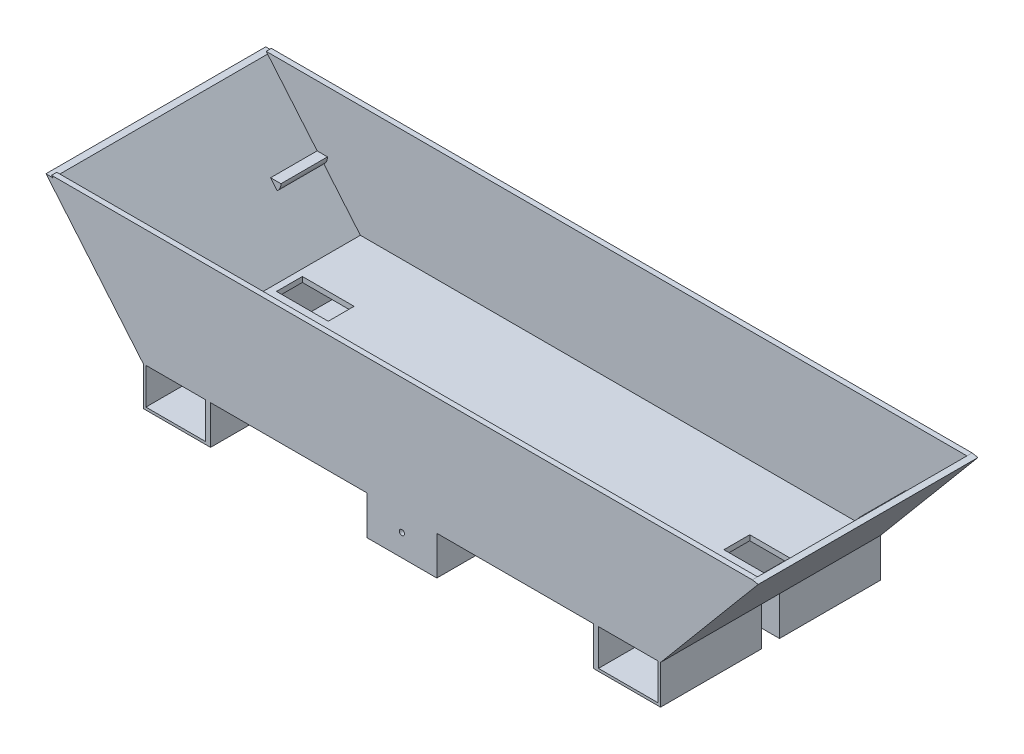
SolidWorks part; units mm, degrees
ref_plane "Plan de face" through (0, 0, 0) normal (0, 0, 1) x (1, 0, 0)
ref_plane "Plan de dessus" through (0, 0, 0) normal (0, 1, 0) x (1, 0, 0)
ref_plane "Plan de droite" through (0, 0, 0) normal (1, 0, 0) x (0, 0, -1)
sketch "Esquisse1" plane through (0, 0, 0) normal (0, 0, 1) x (1, 0, 0)
  line L0 (0, 0) -> (-200, 0)
  line L1 (0, 0) -> (37.7595, 45)
  line L2 (-200, 0) -> (-237.7595, 45)
  point P3 (0, 0)
  point P6 (-225.173, 30)
  point P7 (-225.173, 30)
  point P8 (0, 0)
  dimension "D1" = 130
  dimension "D2" = 130
  dimension "D3" = 200
  dimension "D4" = 45
  dimension "D5" = 45
extrude "Extru.-Mince3" add sketch "Esquisse1" along normal blind 85 thin
sketch "Esquisse2" plane through (0, 0, 0) normal (0, -1, 0) x (-1, 0, 0)
  line L0 (0, -85) -> (200, -85) construction
  line L3 (199.0674, -47) -> (175, -47)
  line L4 (175, -85) -> (175, -47)
  line L5 (0.9326, 0) -> (199.0674, 0) construction
  line L6 (199.0674, -85) -> (199.0674, 0) construction
  line L7 (200, -85) -> (200, 0) construction
  line L8 (0, 0) -> (200, 0) construction
  line L11 (0, -47) -> (25, -47)
  line L12 (25, -85) -> (25, -47)
  line L13 (0.9326, -85) -> (199.0674, -85) construction
  line L16 (87.5, -85) -> (87.5, -47)
  line L17 (87.5, -47) -> (112.5, -47)
  line L18 (112.5, -85) -> (112.5, -47)
  line L23 (199.0674, -38) -> (175, -38)
  line L24 (175, 0) -> (175, -38)
  line L28 (112.5, 0) -> (112.5, -38)
  line L29 (112.5, -38) -> (87.5, -38)
  line L30 (87.5, 0) -> (87.5, -38)
  line L33 (0, -85) -> (0, 0) construction
  line L36 (0, -38) -> (25, -38)
  line L37 (25, 0) -> (25, -38)
  point P0 (200, -85)
  point P10 (0, -85)
  point P16 (100, -85)
  point P21 (200, 0)
  point P27 (100, 0)
  point P34 (0, 0)
  dimension "D1" = 38
  dimension "D2" = 25
  dimension "D3" = 38
  dimension "D4" = 38
  dimension "D5" = 38
  dimension "D6" = 25
  dimension "D7" = 25
  dimension "D8" = 25
  dimension "D9" = 25
  dimension "D10" = 25
  dimension "D11" = 12.5
  dimension "D12" = 12.5
  dimension "D13" = 38
  dimension "D14" = 38
extrude "Extru.-Mince4" add sketch "Esquisse2" along normal blind 14 thin thin type mid plane wall 2
sketch "Esquisse3" plane through (0, 0, 0) normal (0, -1, 0) x (-1, 0, 0)
  line L0 (199.0674, -39) -> (200, -39.0231) construction
  line L1 (200, -85) -> (200, 0) construction
  line L2 (200, -39.0231) -> (200, 0)
extrude "Extru.-Mince5" add sketch "Esquisse3" along normal blind 14 thin thin type one direction reverse wall 1
sketch "Esquisse4" plane through (0, 0, 0) normal (0, -1, 0) x (1, 0, 0)
  line L0 (-199.0674, 46) -> (-200, 46) construction
  line L1 (-200, 85) -> (-200, 39.0231) construction
  line L2 (-200, 85) -> (-200, 46)
extrude "Extru.-Mince6" add sketch "Esquisse4" along normal blind 14 thin thin type one direction reverse wall 1
sketch "Esquisse5" plane through (0, 0, 0) normal (0, -1, 0) x (-1, 0, 0)
  line L0 (0, 0) -> (0, -37)
extrude "Extru.-Mince7" add sketch "Esquisse5" along normal blind 14 thin thin type one direction reverse wall 1
sketch "Esquisse6" plane through (0, 0, 0) normal (0, -1, 0) x (-1, 0, 0)
  line L0 (0, -48) -> (0, -85)
extrude "Extru.-Mince8" add sketch "Esquisse6" along normal blind 14 thin thin type one direction reverse wall 1
sketch "Esquisse9" plane through (0, -14, 0) normal (0, -1, 0) x (-1, 0, 0)
  line L1 (200, -39.0231) -> (174, -39.0231)
  line L2 (200, -39.0231) -> (200, 0)
  line L3 (200, 0) -> (174, 0)
  line L4 (174, -39.0231) -> (174, 0)
  line L5 (174, -46) -> (200, -46)
  line L6 (174, -46) -> (174, -85)
  line L7 (174, -85) -> (200, -85)
  line L8 (200, -46) -> (200, -85)
  line L9 (86.5, -46) -> (113.5, -46)
  line L10 (86.5, -46) -> (86.5, -85)
  line L11 (86.5, -85) -> (113.5, -85)
  line L12 (113.5, -46) -> (113.5, -85)
  line L13 (86.5, -39) -> (113.5, -39)
  line L14 (86.5, -39) -> (86.5, 0)
  line L15 (86.5, 0) -> (113.5, 0)
  line L16 (113.5, -39) -> (113.5, 0)
  line L17 (26, -46) -> (0, -46)
  line L18 (26, -46) -> (26, -85)
  line L19 (26, -85) -> (0, -85)
  line L20 (0, -46) -> (0, -85)
  line L21 (26, -39) -> (0, -39)
  line L22 (26, -39) -> (26, 0)
  line L23 (26, 0) -> (0, 0)
  line L24 (0, -39) -> (0, 0)
extrude "Boss.-Extru.2" add sketch "Esquisse9" along normal blind 1
fillet "Congé1" radius 10 1 edges at (-100, -15, 39)
fillet "Congé2" radius 10 1 edges at (-100, -14, 37)
fillet "Congé3" radius 10 1 edges at (-100, -15, 46)
fillet "Congé4" radius 10 1 edges at (-100, -14, 48)
sketch "Esquisse10" plane through (0, 0, 85) normal (0, 0, 1) x (1, 0, 0)
  line L1 (-111.5, 0) -> (-88.5, 0)
  line L2 (-111.5, 0) -> (-111.5, -14)
  line L3 (-111.5, -14) -> (-88.5, -14)
  line L4 (-88.5, 0) -> (-88.5, -14)
extrude "Boss.-Extru.3" add sketch "Esquisse10" against normal blind 3
sketch "Esquisse11" plane through (0, 0, 0) normal (0, 0, -1) x (-1, 0, 0)
  line L1 (88.5, 0) -> (111.5, 0)
  line L2 (88.5, 0) -> (88.5, -14)
  line L3 (88.5, -14) -> (111.5, -14)
  line L4 (111.5, 0) -> (111.5, -14)
extrude "Boss.-Extru.4" add sketch "Esquisse11" against normal blind 3
sketch "Esquisse13" plane through (0, 0, 0) normal (0, 0, -1) x (-1, 0, 0)
  line L0 (86.5, -15) -> (86.5, 0) construction
  line L2 (113.5, -15) -> (86.5, -15) construction
  circle A0 centre (100, -7.5) radius 1
  dimension "D3" = 2
  dimension "D1" = 13.5
  dimension "D2" = 7.5
sketch "Esquisse14" plane through (0, 0, 0) normal (0, 0, -1) x (-1, 0, 0)
  line L1 (113.5, -15) -> (86.5, -15) construction
  line L3 (86.5, -15) -> (86.5, 0) construction
  circle A0 centre (100, -6.5) radius 1
  dimension "D1" = 8.5
  dimension "D3" = 2
  dimension "D2" = 13.5
extrude "Enlèv. mat.-Extru.2" cut sketch "Esquisse14" against normal blind 15
sketch "Esquisse15" plane through (0, 0, 85) normal (0, 0, 1) x (1, 0, 0)
  line L0 (-86.5, -15) -> (-86.5, 0) construction
  line L1 (-86.5, -15) -> (-113.5, -15) construction
  circle A0 centre (-100, -6.5) radius 1
  dimension "D1" = 13.5
  dimension "D2" = 8.5
  dimension "D3" = 2
extrude "Enlèv. mat.-Extru.4" cut sketch "Esquisse15" against normal blind 15
chamfer "Chanfrein2" distance 2 angle 30 1 edges at (36.2274, 46.2856, 42.5)
chamfer "Chanfrein4" distance 2 angle 48 1 edges at (-236.2274, 46.2856, 42.5)
sketch "Esquisse17" plane through (0, 0, 85) normal (0, 0, 1) x (1, 0, 0)
  line L0 (35.4852, 45.401) -> (-235.4852, 45.401)
  line L1 (-199.0674, 2) -> (-234.9418, 44.7535) construction
  line L20 (-199.0674, 2) -> (-234.9418, 44.7535)
  line L21 (-234.9418, 44.7535) -> (-237.6314, 44.8474)
  line L22 (-237.6314, 44.8474) -> (-200, 0)
  line L23 (-200, 0) -> (-200, -15)
  line L24 (-200, -15) -> (-174, -15)
  line L25 (-174, -15) -> (-174, 0)
  line L26 (-174, 0) -> (-113.5, 0)
  line L27 (-113.5, 0) -> (-113.5, -15)
  line L28 (-113.5, -15) -> (-86.5, -15)
  line L29 (-86.5, -15) -> (-86.5, 0)
  line L30 (-86.5, 0) -> (-26, 0)
  line L31 (-26, 0) -> (-26, -15)
  line L32 (-26, -15) -> (0, -15)
  line L33 (0, -15) -> (0, 0)
  line L34 (0, 0) -> (37.7595, 45)
  line L35 (37.7595, 45) -> (35.4852, 45.401)
  line L36 (35.4852, 45.401) -> (-0.9326, 2)
  line L37 (-0.9326, 2) -> (-199.0674, 2)
  line L38 (-199.0674, 2) -> (-235.4852, 45.401)
  line L54 (35.4852, 45.401) -> (-0.9326, 2)
  line L55 (-0.9326, 2) -> (-199.0674, 2)
  dimension "D1" = 0
extrude "Boss.-Extru.8" add sketch "Esquisse17" against normal blind 2
sketch "Esquisse18" plane through (0, 0, 0) normal (0, 0, -1) x (-1, 0, 0)
  line L0 (-35.4852, 45.401) -> (235.4852, 45.401)
  line L1 (199.0674, 2) -> (234.9418, 44.7535) construction
  line L2 (-35.4852, 45.401) -> (0.9326, 2)
  line L3 (0.9326, 2) -> (199.0674, 2)
  line L4 (199.0674, 2) -> (235.4852, 45.401)
extrude "Boss.-Extru.9" add sketch "Esquisse18" against normal blind 2
sketch "Esquisse23" plane through (0, 0, 0) normal (0, -1, 0) x (-1, 0, 0)
  line L0 (3.5, -37) -> (23.5, -37)
  line L1 (23.5, -37) -> (23.5, -27)
  line L2 (23.5, -27) -> (3.5, -27)
  line L3 (3.5, -27) -> (3.5, -37)
  line L4 (24, -37) -> (1, -37) construction
  line L6 (24, 0) -> (24, -37) construction
  point P7 (23.5, -32)
  dimension "D1" = 10
  dimension "D2" = 0
  dimension "D3" = 20
  dimension "D4" = 0.5
extrude "Enlèv. mat.-Extru.7" cut sketch "Esquisse23" against normal blind 2
sketch "Esquisse24" plane through (0, 0, 0) normal (0, -1, 0) x (1, 0, 0)
  line L1 (-23.5, 48) -> (-3.5, 48)
  line L2 (-23.5, 48) -> (-23.5, 58)
  line L3 (-23.5, 58) -> (-3.5, 58)
  line L4 (-3.5, 48) -> (-3.5, 58)
  line L5 (-24, 48) -> (-1, 48) construction
  line L7 (-24, 85) -> (-24, 48) construction
  dimension "D1" = 0.5
  dimension "D2" = 20
  dimension "D3" = 10
extrude "Enlèv. mat.-Extru.9" cut sketch "Esquisse24" against normal blind 2
sketch "Esquisse25" plane through (0, 0, 0) normal (0, -1, 0) x (-1, 0, 0)
  line L0 (176, -48) -> (199, -48) construction
  line L1 (176.5, -48) -> (196.5, -48)
  line L2 (176.5, -48) -> (176.5, -58)
  line L3 (176.5, -58) -> (196.5, -58)
  line L4 (196.5, -48) -> (196.5, -58)
  line L5 (199, -85) -> (199, -48) construction
  dimension "D1" = 20
  dimension "D2" = 10
  dimension "D3" = 2.5
extrude "Enlèv. mat.-Extru.11" cut sketch "Esquisse25" against normal blind 2
sketch "Esquisse26" plane through (0, 0, 0) normal (0, -1, 0) x (-1, 0, 0)
  line L0 (176, -37) -> (199, -37) construction
  line L1 (176.5, -37) -> (196.5, -37)
  line L2 (176.5, -37) -> (176.5, -27)
  line L3 (176.5, -27) -> (196.5, -27)
  line L4 (196.5, -37) -> (196.5, -27)
  line L6 (176, 0) -> (176, -37) construction
  dimension "D1" = 20
  dimension "D2" = 10
  dimension "D3" = 0.5
extrude "Enlèv. mat.-Extru.13" cut sketch "Esquisse26" against normal blind 2
sketch "Esquisse28" plane through (-115.8327, -97.1952, 0) normal (0.766, 0.6428, 0) x (0, 0, -1)
  line L0 (-83.0445, 155.4901) -> (-65.0445, 155.4901)
  line L1 (-2, 155.4901) -> (-20, 155.4901)
  line L2 (-2, 129.4901) -> (-2, 185.3008) construction
  line L4 (-83, 129.4901) -> (-2, 129.4901) construction
  dimension "D1" = 18
  dimension "D2" = 18
  dimension "D3" = 26
revolve "Révol.-Mince9" add sketch "Esquisse28" angle 50 about L0
sketch "Esquisse29" plane through (-115.8327, -97.1952, 0) normal (0.766, 0.6428, 0) x (0, 0, -1)
  line L0 (-65.0445, 155.4901) -> (-2, 155.4901) construction
  line L1 (-2, 129.4901) -> (-2, 185.3008) construction
  line L2 (-2, 155.4901) -> (-20, 155.4901)
  dimension "D1" = 18
revolve "Révol.-Mince10" add sketch "Esquisse29" angle 50 about L2 wall 4
sketch "Esquisse31" plane through (-1.5321, 1.2856, 0) normal (-0.766, 0.6428, 0) x (0, 0, 1)
  line L0 (2, 26.9326) -> (20, 26.9326)
  line L1 (2, 57.5886) -> (2, 0.9326) construction
  line L2 (83, 26.9326) -> (65, 26.9326)
  line L3 (83, 0.9326) -> (83, 57.5886) construction
  line L4 (83, 0.9326) -> (2, 0.9326) construction
  dimension "D1" = 26
  dimension "D2" = 18
  dimension "D3" = 18
revolve "Révol.-Mince11" add sketch "Esquisse31" angle 50 about L0
sketch "Esquisse32" plane through (-1.5321, 1.2856, 0) normal (-0.766, 0.6428, 0) x (0, 0, 1)
  line L0 (83, 26.9326) -> (65, 26.9326)
  line L1 (83, 0.9326) -> (83, 57.5886) construction
  line L2 (83, 0.9326) -> (2, 0.9326) construction
  dimension "D1" = 18
  dimension "D2" = 26
revolve "Révol.-Mince12" add sketch "Esquisse32" angle 50 about L0 wall 4
